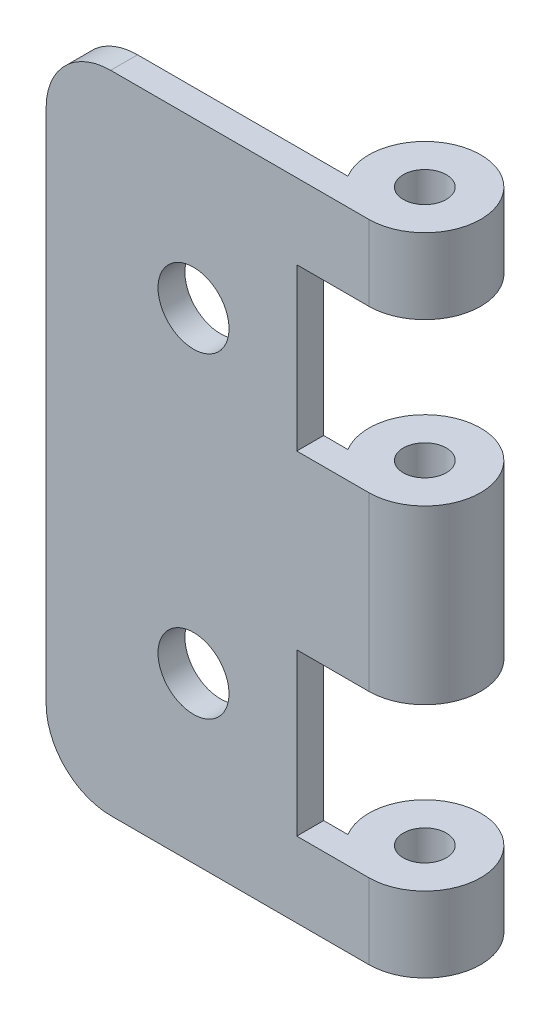
SolidWorks part; units mm, degrees
ref_plane "Front Plane" through (0, 0, 0) normal (0, 0, 1) x (1, 0, 0)
ref_plane "Top Plane" through (0, 0, 0) normal (0, 1, 0) x (1, 0, 0)
ref_plane "Right Plane" through (0, 0, 0) normal (1, 0, 0) x (0, 0, -1)
sketch "Sketch1" plane through (0, 0, 0) normal (0, 1, 0) x (1, 0, 0)
  line L0 (29.591, 3.175) -> (32.456, 3.175)
  line L1 (0, 0) -> (29.591, 0)
  line L2 (0, 0) -> (0, 3.175)
  line L3 (0, 3.175) -> (29.591, 3.175)
  line L4 (29.591, 0) -> (29.591, 3.175)
  line L5 (29.591, 0) -> (38.1, 0)
  circle A0 centre (38.1, 6.604) radius 6.604
  dimension "D3" = 13.208
  dimension "D1" = 3.175
  dimension "D2" = 29.591
  dimension "D4" = 38.1
extrude "Boss-Extrude1" add sketch "Sketch1" along normal blind 76.2 contours L1 L4 L3 L2 | A0 L0 L4 L5 | A0 region at (14.7955, 0, -1.5875) region at (32.0358, 0, -1.3339) region at (38.1, 0, -6.604)
sketch "Sketch2" plane through (0, 0, -3.175) normal (0, 0, -1) x (-1, 0, 0)
  line L0 (0, 76.2) -> (-32.456, 76.2) construction
  line L1 (0, 76.2) -> (0, 0) construction
  line L2 (0, 0) -> (-32.456, 0) construction
  circle A0 centre (-17.399, 56.769) radius 4.191
  circle A1 centre (-17.399, 19.431) radius 4.191
  dimension "D1" = 8.382
  dimension "D4" = 8.382
  dimension "D2" = 19.431
  dimension "D3" = 17.399
  dimension "D5" = 19.431
  dimension "D6" = 17.399
extrude "Cut-Extrude1" cut sketch "Sketch2" against normal blind 50.8
extrude "Cut-Extrude2" cut sketch "Sketch1<3>" along normal blind 19.05 from offset 8.89 contours A0 L0 L4 L5 | A0 region at (32.0358, 0, -1.3339) region at (38.1, 0, -6.604)
sketch "Sketch1<3>" plane through (0, 0, 0) normal (0, 1, 0) x (1, 0, 0) same geometry as "Sketch1"
extrude "Cut-Extrude3" cut sketch "Sketch1<5>" against normal blind 19.05 from offset 67.31 contours A0 | A0 L0 L4 L5 region at (32.0358, 0, -1.3339) region at (38.1, 0, -6.604)
sketch "Sketch1<5>" plane through (0, 0, 0) normal (0, 1, 0) x (1, 0, 0) same geometry as "Sketch1"
sketch "Sketch3" plane through (0, 76.2, 0) normal (0, 1, 0) x (1, 0, 0)
  arc A0 (38.1, 0) -> (32.456, 3.175) centre (38.1, 6.604) ccw construction
  arc A1 (38.1, 0) -> (32.456, 3.175) centre (38.1, 6.604) ccw
  circle A2 centre (38.1, 6.604) radius 2.54
  dimension "D1" = 5.08
extrude "Cut-Extrude4" cut sketch "Sketch3" against normal through all contours A2 region at (38.1, 76.2, -6.604)
fillet "Fillet1" radius 7.62 1 edges at (0, 0, -1.5875) type face fillet first side face at (0, 38.1, -1.5875) second side face at (38.1, 0, -4.064)
fillet "Fillet2" radius 7.62 1 edges at (0, 76.2, -1.5875) type face fillet first side face at (38.1, 76.2, -4.064) second side face at (0, 41.91, -1.5875)
